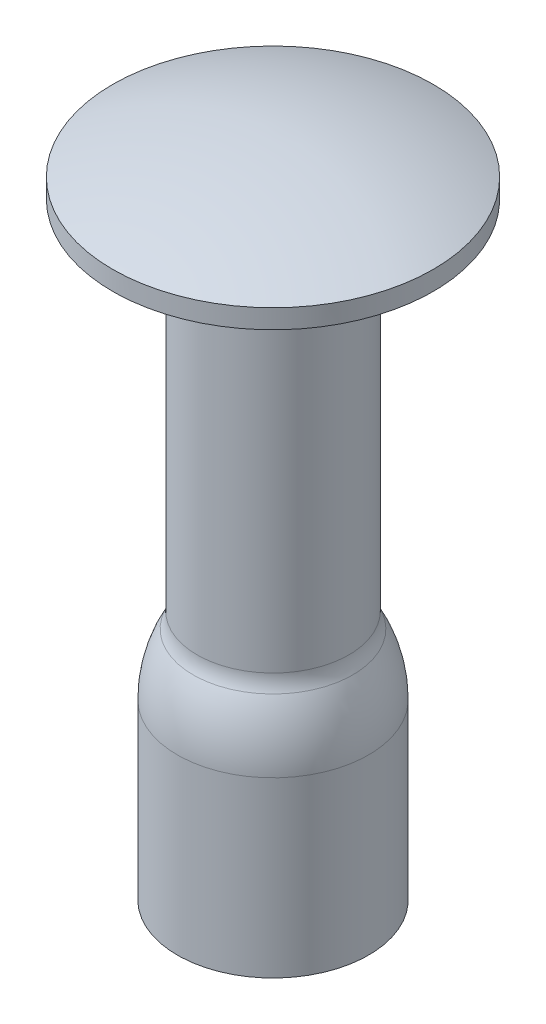
SolidWorks part; units mm, degrees
ref_plane "Front Plane" through (0, 0, 0) normal (0, 0, 1) x (1, 0, 0)
ref_plane "Top Plane" through (0, 0, 0) normal (0, 1, 0) x (1, 0, 0)
ref_plane "Right Plane" through (0, 0, 0) normal (1, 0, 0) x (0, 0, -1)
ref_axis "Axis1" through (0, -13.2213, 0) along (0, 1, 0)
sketch "Sketch1" plane through (0, 0, 0) normal (0, 0, 1) x (1, 0, 0)
  line L0 (1.3, -6.8046) -> (1.3, -9.525)
  line L1 (0, 0.8128) -> (0, -9.525) construction
  line L2 (2.5146, 0.3) -> (2.5146, 0)
  line L3 (2.5146, 0) -> (1.1906, 0)
  line L4 (1.1906, 0) -> (1.1906, -5.6)
  line L5 (0, 0) -> (0, 0.8128)
  line L6 (0.9906, -5.6) -> (0.9906, 0)
  line L7 (0.9906, 0) -> (0, 0)
  line L8 (1.5, -6.8046) -> (1.5, -9.525)
  line L9 (1.3, -9.525) -> (1.5, -9.525)
  line L10 (1.25, -5.9) -> (9.748, -5.9) construction
  line L11 (1.25, -5.9) -> (1.25, 0) construction
  line L12 (1.25, 0) -> (9.9319, 0) construction
  arc A0 (1.1906, -5.6) -> (1.2525, -5.8409) centre (1.6906, -5.6) ccw
  arc A1 (1.2525, -5.8409) -> (1.5, -6.8046) centre (-0.5, -6.8046) cw
  arc A2 (1.3, -6.8046) -> (1.0773, -5.9373) centre (-0.5, -6.8046) ccw
  arc A3 (1.0773, -5.9373) -> (0.9906, -5.6) centre (1.6906, -5.6) cw
  arc A4 (0, 0.8128) -> (2.5146, 0.3) centre (0, -5.609) cw
  point P20 (0.9906, -2.8)
  point P21 (1.5, -5.06)
  dimension "D6" = 0.5
  dimension "D8" = 2
  dimension "D1" = 5.0292
  dimension "D2" = 0.8128
  dimension "D3" = 0.3
  dimension "D4" = 2.3813
  dimension "D5" = 0.2
  dimension "D7" = 9.525
  dimension "D9" = 3
  dimension "D10" = 5.9
  dimension "D11" = 2.5
  dimension "D12" = 0.3
revolve "Revolve1" add sketch "Sketch1" angle 360 about L1
